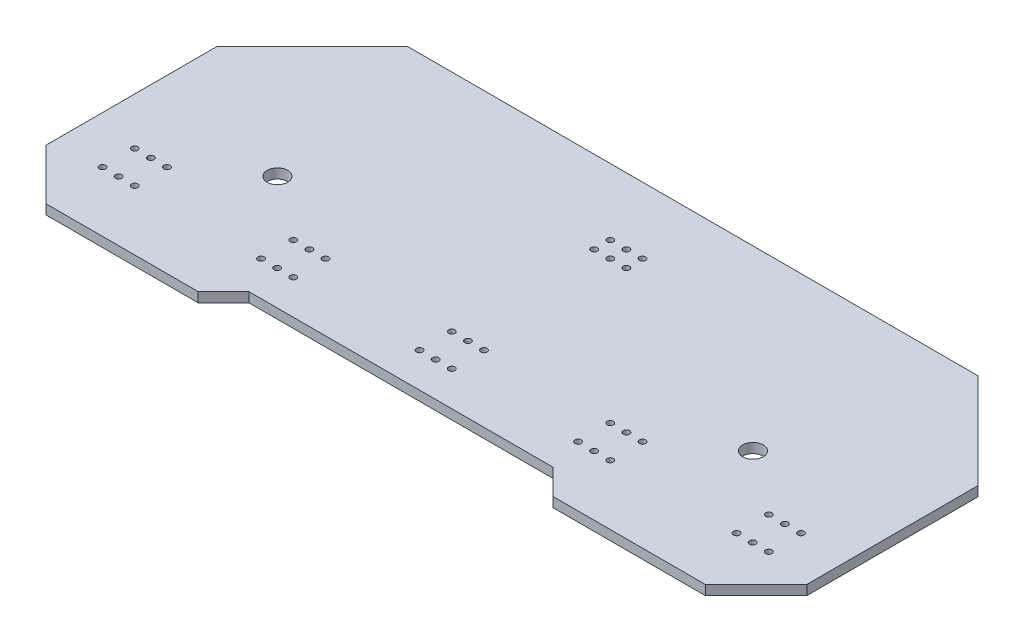
SolidWorks part; units mm, degrees
ref_plane "Front Plane" through (0, 0, 0) normal (0, 0, 1) x (1, 0, 0)
ref_plane "Top Plane" through (0, 0, 0) normal (0, 1, 0) x (1, 0, 0)
ref_plane "Right Plane" through (0, 0, 0) normal (1, 0, 0) x (0, 0, -1)
sketch "Sketch1" plane through (0, 0, 0) normal (0, 1, 0) x (1, 0, 0)
  line L0 (0, 0) -> (0, 13) construction
  line L1 (-60, -22) -> (60, -22)
  line L2 (-60, -22) -> (-60, 28)
  line L3 (-60, 28) -> (60, 28)
  line L4 (60, -22) -> (60, 28)
  line L5 (0, 0) -> (60, 28) construction
  line L6 (-60, 28) -> (0, 0) construction
  line L11 (0, 13) -> (0, 28) construction
  point P0 (0, 0)
  dimension "D1" = 120
  dimension "D2" = 28
  dimension "D6" = 22
extrude "Boss-Extrude1" add sketch "Sketch1" along normal blind 1.53
sketch "Sketch2" plane through (0, 1.53, 0) normal (0, 1, 0) x (1, 0, 0)
  line L0 (0, -10) -> (4.8827, -10) construction
  line L24 (-2.54, -7.46) -> (0, -7.46) construction
  line L25 (0, -7.46) -> (2.54, -7.46) construction
  line L26 (0, -7.46) -> (0, -12.54) construction
  line L27 (0, -12.54) -> (2.54, -12.54) construction
  line L28 (0, -12.54) -> (-2.54, -12.54) construction
  line L29 (0, -7.46) -> (0, 0) construction
  circle A25 centre (-2.54, -7.46) radius 0.5
  circle A26 centre (0, -7.46) radius 0.5
  circle A27 centre (2.54, -7.46) radius 0.5
  circle A28 centre (-2.54, -12.54) radius 0.5
  circle A29 centre (0, -12.54) radius 0.5
  circle A30 centre (2.54, -12.54) radius 0.5
  point P2 (0, -7.46)
  dimension "D1" = 10
  dimension "D2" = 1
  dimension "D8" = 5.08
  dimension "D9" = 2.54
extrude "PushButtonHoles" cut sketch "Sketch2" against normal through all
sketch "Sketch7" plane through (0, 1.53, 0) normal (0, 1, 0) x (1, 0, 0)
  line L0 (-37.5, 0) -> (0, 0) construction
  line L1 (0, 0) -> (37.5, 0) construction
  circle A0 centre (-37.5, 0) radius 1.625
  circle A1 centre (37.5, 0) radius 1.625
  dimension "D1" = 3.25
  dimension "D2" = 37.5
extrude "Mount Holes" cut sketch "Sketch7" against normal through all
sketch "Sketch5" plane through (0, 1.53, 0) normal (0, 1, 0) x (1, 0, 0)
  line L0 (-2.54, 17.54) -> (0, 17.54) construction
  line L1 (0, 17.54) -> (2.54, 17.54) construction
  line L2 (0, 17.54) -> (0, 15) construction
  line L3 (0, 15) -> (2.54, 15) construction
  line L4 (0, 15) -> (-2.54, 15) construction
  line L5 (0, 0) -> (0, 15) construction
  circle A0 centre (-2.54, 17.54) radius 0.5
  circle A1 centre (0, 17.54) radius 0.5
  circle A2 centre (2.54, 17.54) radius 0.5
  circle A3 centre (-2.54, 15) radius 0.5
  circle A4 centre (0, 15) radius 0.5
  circle A5 centre (2.54, 15) radius 0.5
  dimension "D1" = 2.54
  dimension "D2" = 2.54
  dimension "D3" = 15
extrude "RJ12Holes" cut sketch "Sketch5" against normal through all
sketch "Sketch6" plane through (0, 1.53, 0) normal (0, 1, 0) x (1, 0, 0)
  line L0 (-45, 28) -> (-60, 13)
  line L1 (60, 28) -> (-60, 28) construction
  line L2 (-60, 28) -> (-60, -22) construction
  line L3 (-60, 13) -> (-60, -14)
  line L4 (-60, -14) -> (-52, -22)
  line L5 (-60, -22) -> (60, -22) construction
  line L6 (-52, -22) -> (-28, -22)
  line L7 (-28, -22) -> (-24, -18)
  line L8 (-24, -18) -> (24, -18)
  line L9 (24, -18) -> (28, -22)
  line L10 (28, -22) -> (52, -22)
  line L11 (52, -22) -> (60, -14)
  line L12 (60, -22) -> (60, 28) construction
  line L13 (60, -14) -> (60, 13)
  line L14 (60, 13) -> (45, 28)
  line L15 (45, 28) -> (-45, 28)
  line L16 (0, 0) -> (0, -18) construction
  line L17 (0, 0) -> (0, 28) construction
  line L19 (-70.5255, -34.7658) -> (70.5255, -34.7658)
  line L20 (-70.5255, -34.7658) -> (-70.5255, 34.7658)
  line L21 (-70.5255, 34.7658) -> (70.5255, 34.7658)
  line L22 (70.5255, -34.7658) -> (70.5255, 34.7658)
  line L23 (-70.5255, -34.7658) -> (70.5255, 34.7658) construction
  line L24 (-70.5255, 34.7658) -> (70.5255, -34.7658) construction
  dimension "D1" = 45
  dimension "D2" = 45
  dimension "D3" = 90
  dimension "D4" = 14
  dimension "D5" = 18
  dimension "D6" = 24
extrude "Cut-Extrude4" cut sketch "Sketch6" against normal through all
pattern_linear "LPattern1" count 3 spacing 25 along (1, 0, 0) count 3 spacing 25 along (-1, 0, 0) of "PushButtonHoles" pattern seed only yes
